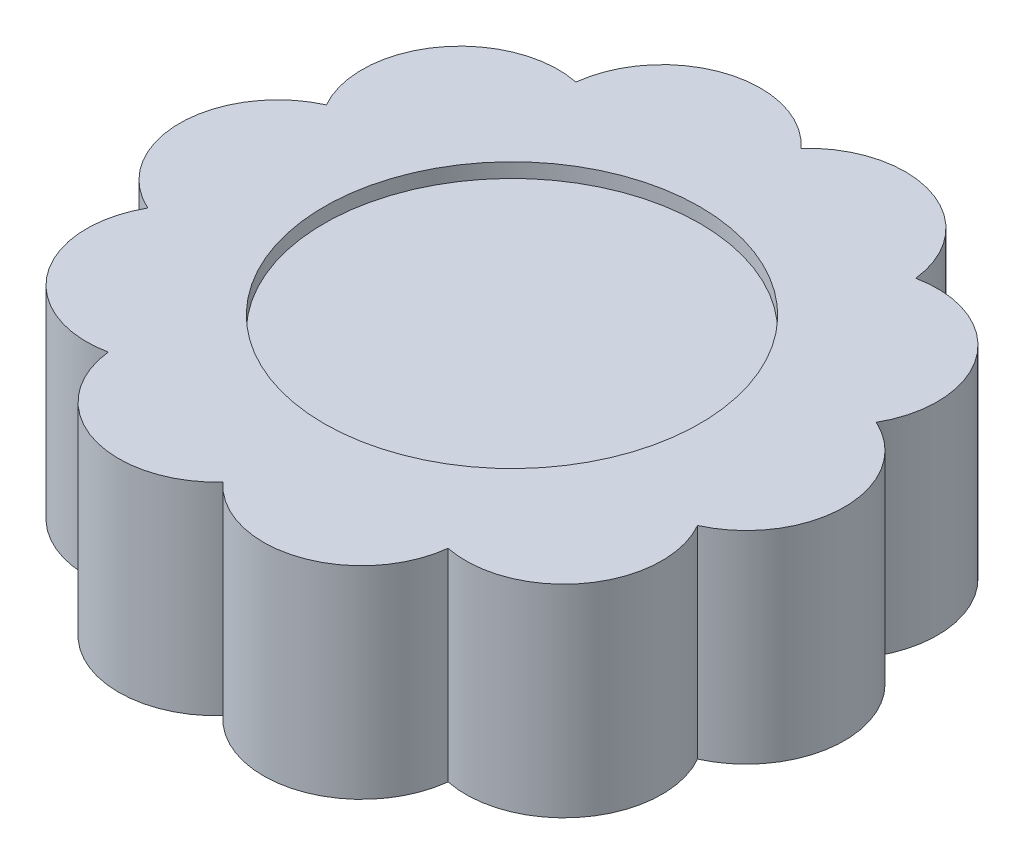
SolidWorks part; units mm, degrees
ref_plane "Спереди" through (0, 0, 0) normal (0, 0, 1) x (1, 0, 0)
ref_plane "Сверху" through (0, 0, 0) normal (0, 1, 0) x (1, 0, 0)
ref_plane "Справа" through (0, 0, 0) normal (1, 0, 0) x (0, 0, -1)
sketch "Эскиз1" plane through (0, 0, 0) normal (0, 1, 0) x (1, 0, 0)
  line L0 (-1.5, 2.5981) -> (-1.5, -2.5981) construction
  line L1 (-1.5, 2.5981) -> (-1.5, -2.5981) construction
  line L2 (-1.6, 2.6552) -> (-1.6, -2.6552)
  arc A0 (0, 3) -> (-1.5, 2.5981) centre (0, 0) ccw construction
  arc A1 (0, -3) -> (0, 3) centre (0, 0) ccw construction
  arc A2 (-1.5, -2.5981) -> (0, -3) centre (0, 0) ccw construction
  arc A3 (0, 3) -> (-1.5, 2.5981) centre (0, 0) ccw construction
  arc A4 (0, -3) -> (0, 3) centre (0, 0) ccw construction
  arc A5 (-1.5, -2.5981) -> (0, -3) centre (0, 0) ccw construction
  circle A6 centre (0, 0) radius 5
  arc A7 (0, 3.1) -> (-1.6, 2.6552) centre (0, 0) ccw
  arc A8 (-1.6, -2.6552) -> (0, -3.1) centre (0, 0) ccw
  arc A9 (0, -3.1) -> (0, 3.1) centre (0, 0) ccw
  dimension "D1" = 10
  dimension "D2" = 0.1
extrude "Бобышка-Вытянуть1" add sketch "Эскиз1" along normal up to surface (6.5 mm away)
sketch "Эскиз2" plane through (0, 0, 0) normal (0, -1, 0) x (1, 0, 0)
  circle A0 centre (0, 0) radius 5 construction
  circle A1 centre (0, 0) radius 5
  circle A4 centre (0, 0) radius 4
  circle A5 centre (0, 0) radius 4
  dimension "D1" = 1
extrude "Бобышка-Вытянуть2" add sketch "Эскиз2" along normal blind 3
sketch "Эскиз3" plane through (0, 6.5, 0) normal (0, 1, 0) x (1, 0, 0)
  circle A0 centre (0, 0) radius 5 construction
  circle A1 centre (0, 0) radius 5
extrude "Бобышка-Вытянуть3" add sketch "Эскиз3" along normal blind 1
sketch "Эскиз4" plane through (0, 7.5, 0) normal (0, 1, 0) x (1, 0, 0)
  circle A0 centre (0, 0) radius 10
  circle A1 centre (0, 0) radius 5 construction
  circle A2 centre (0, 0) radius 5
  dimension "D1" = 20
extrude "Бобышка-Вытянуть4" add sketch "Эскиз4" against normal blind 7
sketch "Эскиз5" plane through (0, 7.5, 0) normal (0, 1, 0) x (1, 0, 0)
  line L5 (0, 0) -> (0, 10) construction
  circle A1 centre (0, 0) radius 10 construction
  arc A2 (0, 10) -> (5.8779, 8.0902) centre (0, 0) cw
  arc A3 (0, 10) -> (5.8779, 8.0902) centre (2.5047, 7.7086) cw
  arc A4 (5.8779, 8.0902) -> (9.5106, 3.0902) centre (6.5573, 4.7642) cw
  arc A5 (5.8779, 8.0902) -> (9.5106, 3.0902) centre (0, 0) cw
  arc A6 (9.5106, 3.0902) -> (9.5106, -3.0902) centre (8.1053, 0) cw
  arc A7 (9.5106, 3.0902) -> (9.5106, -3.0902) centre (0, 0) cw
  arc A8 (9.5106, -3.0902) -> (5.8779, -8.0902) centre (6.5573, -4.7642) cw
  arc A9 (9.5106, -3.0902) -> (5.8779, -8.0902) centre (0, 0) cw
  arc A10 (5.8779, -8.0902) -> (0, -10) centre (2.5047, -7.7086) cw
  arc A11 (5.8779, -8.0902) -> (0, -10) centre (0, 0) cw
  arc A12 (0, -10) -> (-5.8779, -8.0902) centre (-2.5047, -7.7086) cw
  arc A13 (0, -10) -> (-5.8779, -8.0902) centre (0, 0) cw
  arc A14 (-5.8779, -8.0902) -> (-9.5106, -3.0902) centre (-6.5573, -4.7642) cw
  arc A15 (-5.8779, -8.0902) -> (-9.5106, -3.0902) centre (0, 0) cw
  arc A16 (-9.5106, -3.0902) -> (-9.5106, 3.0902) centre (-8.1053, 0) cw
  arc A17 (-9.5106, -3.0902) -> (-9.5106, 3.0902) centre (0, 0) cw
  arc A18 (-9.5106, 3.0902) -> (-5.8779, 8.0902) centre (-6.5573, 4.7642) cw
  arc A19 (-9.5106, 3.0902) -> (-5.8779, 8.0902) centre (0, 0) cw
  arc A20 (-5.8779, 8.0902) -> (0, 10) centre (-2.5047, 7.7086) cw
  arc A21 (-5.8779, 8.0902) -> (0, 10) centre (0, 0) cw
  point P8 (3.5537, 10.9371)
  point P9 (3.0902, 9.5106)
  point P40 (0, 0)
  circle M6 centre (0, 0) radius 10
  dimension "D1" = 6.2832
  dimension "D2" = 1.5
  dimension "D3" = 10
extrude "Бобышка-Вытянуть5" add sketch "Эскиз5" against normal up to surface (7 mm away) contours A16 M6 | A20 M6 | A4 M6 | A6 M6 | A8 M6 | A10 M6 | A12 M6 | A14 M6 | A18 A19 | A3 A2 region at (-3.2496, 7.5, -10.0013) region at (8.5076, 7.5, -6.1811) region at (10.516, 7.5, 0) region at (-10.516, 7.5, 0) region at (8.5076, 7.5, 6.1811) region at (-8.5076, 7.5, 6.1811) region at (3.2496, 7.5, 10.0013) region at (-3.2496, 7.5, 10.0013) up to face at (0, 0.5, 5)
sketch "Эскиз6" plane through (0, 7.5, 0) normal (0, 1, 0) x (1, 0, 0)
  circle A0 centre (0, 0) radius 6.5
  dimension "D1" = 13
extrude "Вырез-Вытянуть1" cut sketch "Эскиз6" against normal blind 0.5
